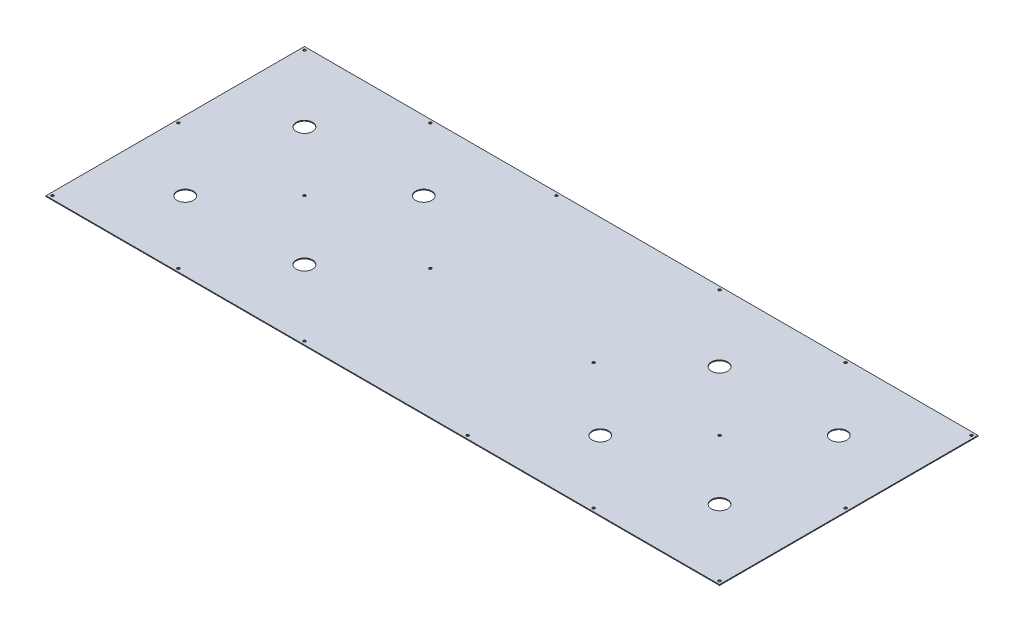
SolidWorks part; units mm, degrees
ref_plane "Front Plane" through (0, 0, 0) normal (0, 0, 1) x (1, 0, 0)
ref_plane "Top Plane" through (0, 0, 0) normal (0, 1, 0) x (1, 0, 0)
ref_plane "Right Plane" through (0, 0, 0) normal (1, 0, 0) x (0, 0, -1)
sketch "main_plate" plane through (0, 0, 0) normal (0, 1, 0) x (1, 0, 0)
  line L1 (-417, 160) -> (417, 160)
  line L2 (-417, 160) -> (-417, -160)
  line L3 (-417, -160) -> (417, -160)
  line L4 (417, 160) -> (417, -160)
  line L5 (-417, 160) -> (417, -160) construction
  line L6 (-417, -160) -> (417, 160) construction
  point P0 (0, 0)
  dimension "D1" = 320
  dimension "D2" = 834
extrude "Boss-Extrude1" add sketch "main_plate" along normal blind 1.016
sketch "main_holes" plane through (0, 1.016, 0) normal (0, 1, 0) x (1, 0, 0)
  line L0 (-417, 160) -> (-417, -160) construction
  line L1 (417, 160) -> (-417, 160) construction
  line L2 (-417, 0) -> (417, 0) construction
  line L3 (417, -160) -> (417, 160) construction
  line L4 (-417, -160) -> (417, -160) construction
  line L5 (0, 160) -> (0, -160) construction
  circle A0 centre (-413, 156) radius 1.6
  circle A6 centre (-257, 156) radius 1.6
  circle A7 centre (-101, 156) radius 1.6
  circle A8 centre (-257, 0) radius 1.6
  circle A9 centre (-101, 0) radius 1.6
  circle A10 centre (-257, -156) radius 1.6
  circle A11 centre (-101, -156) radius 1.6
  circle A12 centre (-413, 0) radius 1.6
  circle A13 centre (-413, -156) radius 1.6
  circle A18 centre (413, -156) radius 1.6
  circle A19 centre (413, 0) radius 1.6
  circle A20 centre (101, -156) radius 1.6
  circle A21 centre (257, -156) radius 1.6
  circle A22 centre (101, 0) radius 1.6
  circle A23 centre (257, 0) radius 1.6
  circle A24 centre (101, 156) radius 1.6
  circle A25 centre (257, 156) radius 1.6
  circle A28 centre (413, 156) radius 1.6
  point P14 (0, 0)
  dimension "D3" = 3.2
  dimension "D1" = 4
  dimension "D2" = 4
  dimension "D4" = 3
  dimension "D5" = 3
extrude "Cut-Extrude1" cut sketch "main_holes" against normal through all
sketch "sma" plane through (0, 1.016, 0) normal (0, 1, 0) x (1, 0, 0)
  line L0 (0, 160) -> (0, -160) construction
  line L1 (417, 160) -> (-417, 160) construction
  line L2 (-417, -160) -> (417, -160) construction
  circle A0 centre (-330.8187, 73.8188) radius 10
  circle A1 centre (-183.1812, 73.8188) radius 10
  circle A2 centre (-183.1812, -73.8187) radius 10
  circle A3 centre (-330.8187, -73.8187) radius 10
  circle A4 centre (-257, 0) radius 1.6 construction
  circle A5 centre (330.8187, -73.8187) radius 10
  circle A6 centre (183.1812, -73.8187) radius 10
  circle A7 centre (183.1812, 73.8188) radius 10
  circle A8 centre (330.8187, 73.8188) radius 10
  dimension "D1" = 20
  dimension "D4" = 73.8188
  dimension "D5" = 73.8188
  dimension "D2" = 2
  dimension "D3" = 2
extrude "Cut-Extrude2" cut sketch "sma" against normal through all
sketch "Sketch4" plane through (0, 1.016, 0) normal (0, 1, 0) x (1, 0, 0)
  circle A0 centre (-495.9535, 13.7799) radius 1.6
  circle A1 centre (-475.9535, 13.7799) radius 1.6
  circle A2 centre (-475.9535, -6.2201) radius 1.6
  circle A3 centre (-495.9535, -6.2201) radius 1.6
  circle A4 centre (-485.9535, 3.7799) radius 12
  point P4 (-514.9144, 13.342)
  point P11 (0, 0)
  point P12 (0, 0)
  point P13 (0, 0)
  point P14 (0, 0)
  point P15 (-485.9535, 3.7799)
  dimension "D1" = 3.2
  dimension "D2" = 2
  dimension "D4" = 24
  dimension "D5" = 10
  dimension "D6" = 10
  dimension "D7" = 10
  dimension "D8" = 10
  dimension "D3" = 2
other "AlignGroup1"
